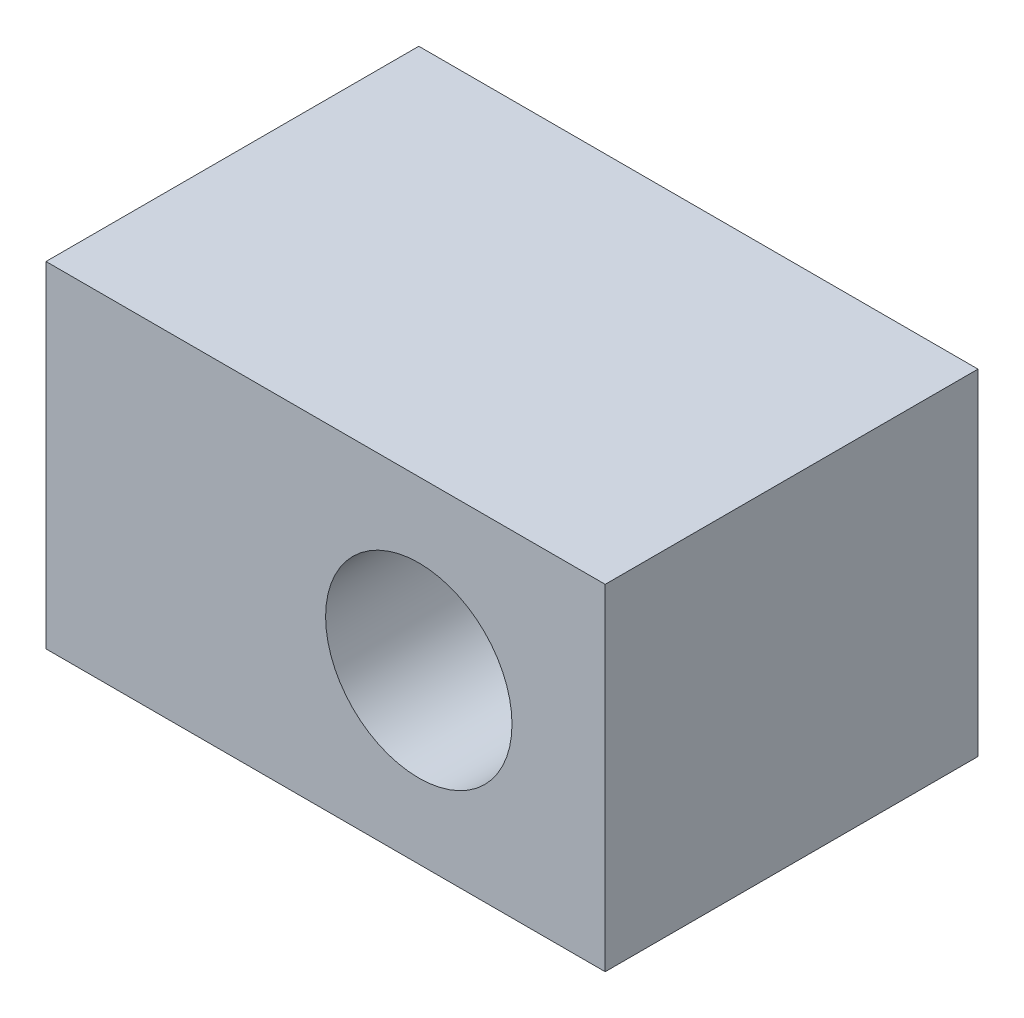
SolidWorks part; units mm, degrees
material "6061-T6 (SS)"
ref_plane "Front Plane" through (0, 0, 0) normal (0, 0, 1) x (1, 0, 0)
ref_plane "Top Plane" through (0, 0, 0) normal (0, 1, 0) x (1, 0, 0)
ref_plane "Right Plane" through (0, 0, 0) normal (1, 0, 0) x (0, 0, -1)
sketch "Sketch1" plane through (0, 0, 0) normal (0, 0, 1) x (1, 0, 0)
  line L4 (-9.525, -5.715) -> (9.525, -5.715)
  line L5 (-9.525, -5.715) -> (-9.525, 5.715)
  line L6 (-9.525, 5.715) -> (9.525, 5.715)
  line L7 (9.525, -5.715) -> (9.525, 5.715)
  line L8 (-9.525, -5.715) -> (9.525, 5.715) construction
  line L9 (-9.525, 5.715) -> (9.525, -5.715) construction
  point P0 (0, 0)
  dimension "D1" = 11.43
  dimension "D2" = 19.05
extrude "Boss-Extrude1" add sketch "Sketch1" along normal blind 12.7
sketch "Sketch3" plane through (0, 0, 12.7) normal (0, 0, 1) x (1, 0, 0)
  line L0 (9.525, -5.715) -> (9.525, 5.715) construction
  circle A0 centre (3.175, 0) radius 3.175
  dimension "D1" = 6.35
  dimension "D2" = 6.35
extrude "Cut-Extrude1" cut sketch "Sketch3" against normal through all
sketch "Sketch8" plane through (-9.525, 0, 0) normal (-1, 0, 0) x (0, 0, 1)
  line L0 (0, 5.715) -> (0, -5.715) construction
  line L3 (12.7, 5.715) -> (0, 5.715) construction
  circle A0 centre (6.35, 0) radius 2.4892
  point P4 (0, 0)
  point P7 (6.35, 5.715)
  dimension "D1" = 4.9784
hole_wizard "#10-32 Tapped Hole3" positions "3DSketch6" profile "Sketch13" tap size "#10-32" standard "ANSI Inch"
sketch3d "3DSketch6"
  point P0 (-9.525, 0, 6.35)
sketch "Sketch13" plane through (-9.525, 0, 6.35) normal (0, 1, 0) x (0, 0, 1)
  line L0 (0, 0) -> (0, 8.6708)
  line L1 (0, 8.6708) -> (2.0193, 7.4574)
  line L2 (2.0193, 7.4574) -> (2.0193, 0)
  line L5 (2.0193, 0) -> (0, 0)
  line L10 (0, 8.6708) -> (-2.0193, 7.4574) construction
  line L11 (0, -6.35) -> (0, 107.95) construction
  dimension "Tap Drill Dia." = 4.0386
  dimension "Tap Drill Depth" = 7.4574
  dimension "Drill Angle" = 118
cosmetic thread "Hole Thread5"
